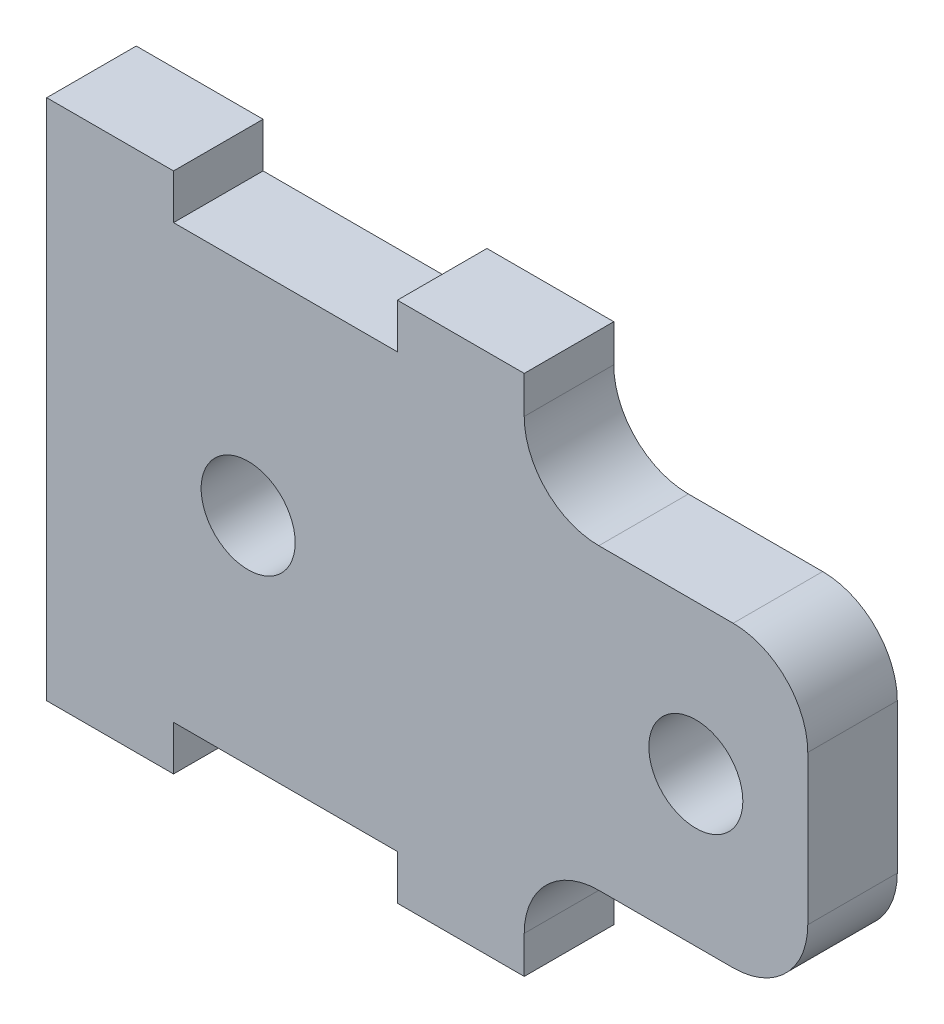
SolidWorks part; units mm, degrees
ref_plane "Plano frontal" through (0, 0, 0) normal (0, 0, 1) x (1, 0, 0)
ref_plane "Plano superior" through (0, 0, 0) normal (0, 1, 0) x (1, 0, 0)
ref_plane "Plano direito" through (0, 0, 0) normal (1, 0, 0) x (0, 0, -1)
sketch "Esboço1" plane through (0, 0, 0) normal (0, 0, 1) x (1, 0, 0)
  line L0 (-15, 0) -> (15, 0) construction
  line L1 (-28.5, -17.5) -> (22.5, -17.5)
  line L2 (-28.5, -17.5) -> (-28.5, 17.5)
  line L3 (-28.5, 17.5) -> (22.5, 17.5)
  line L4 (22.5, -17.5) -> (22.5, 17.5)
  line L5 (-28.5, -17.5) -> (22.5, 17.5) construction
  line L6 (-28.5, 17.5) -> (22.5, -17.5) construction
  line L7 (-5, 14.5) -> (-20, 14.5)
  line L8 (-5, 14.5) -> (-5, 17.5)
  line L9 (-5, 17.5) -> (-20, 17.5)
  line L10 (-20, 14.5) -> (-20, 17.5)
  line L11 (-5, 14.5) -> (-20, 17.5) construction
  line L12 (-5, 17.5) -> (-20, 14.5) construction
  line L13 (-5, -17.5) -> (-20, -17.5)
  line L14 (-20, -14.5) -> (-20, -17.5)
  line L15 (-5, -14.5) -> (-20, -14.5)
  line L16 (-5, -14.5) -> (-5, -17.5)
  line L17 (3.5, 17.5) -> (3.5, 10)
  line L18 (3.5, 10) -> (22.5, 10)
  line L19 (3.5, -17.5) -> (3.5, -10)
  line L20 (3.5, -10) -> (22.5, -10)
  circle A0 centre (-15, 0) radius 3.15
  circle A1 centre (15, 0) radius 3.15
  point P0 (0, 0)
  point P6 (0, 18.5)
  point P13 (0, 0)
  point P28 (22.5, 0)
  dimension "D5" = 6.3
  dimension "D1" = 35
  dimension "D2" = 15
  dimension "D3" = 30
  dimension "D4" = 3
  dimension "D6" = 7.5
  dimension "D7" = 13.5
  dimension "D8" = 8.5
  dimension "D9" = 8.5
  dimension "D10" = 10
extrude "Ressalto-extrusão1" add sketch "Esboço1" along normal blind 6 contours L15 L16 L1 L4 L3 L8 L7 L10 L2 L14 A0 region at (-5.888, 0, 0)
fillet "Filete1" radius 5 4 edges at (3.5, -10, 3) (22.5, -10, 3) (22.5, 10, 3) (3.5, 10, 3)
